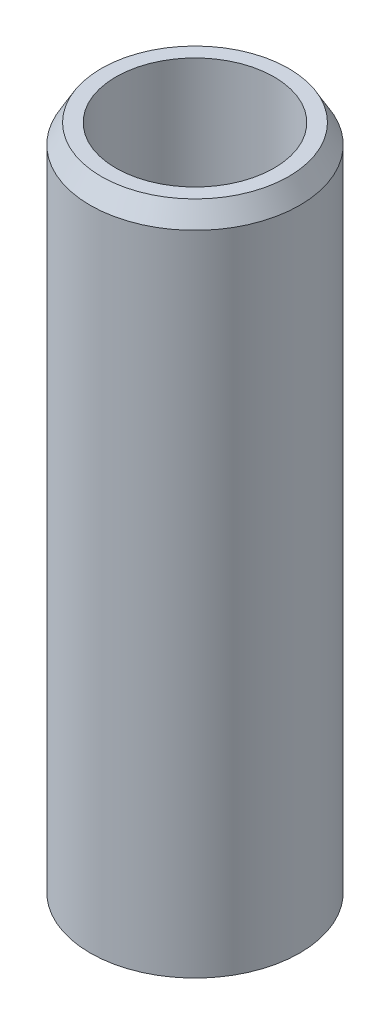
SolidWorks part; units mm, degrees
ref_plane "Front Plane" through (0, 0, 0) normal (0, 0, 1) x (1, 0, 0)
ref_plane "Top Plane" through (0, 0, 0) normal (0, 1, 0) x (1, 0, 0)
ref_plane "Right Plane" through (0, 0, 0) normal (1, 0, 0) x (0, 0, -1)
sketch "Sketch1" plane through (0, 0, 0) normal (0, 1, 0) x (1, 0, 0)
  circle A0 centre (0, 0) radius 32.5
  dimension "SHAFT_OD" = 65
extrude "Boss-Extrude1" add sketch "Sketch1" along normal blind 210.219
sketch "Sketch2" plane through (0, 0, 0) normal (0, 1, 0) x (1, 0, 0)
  circle A0 centre (0, 0) radius 24.5213
  dimension "BORE_D" = 49.0426
extrude "Cut-Extrude1" cut sketch "Sketch2" along normal through all
chamfer "Chamfer1" distance 5.9852 angle 30 2 edges at (0, 210.219, 32.5) (0, 0, 32.5) first distance on face at (0, 210.219, 32.5) first distance on face at (0, 0, 24.5213)
